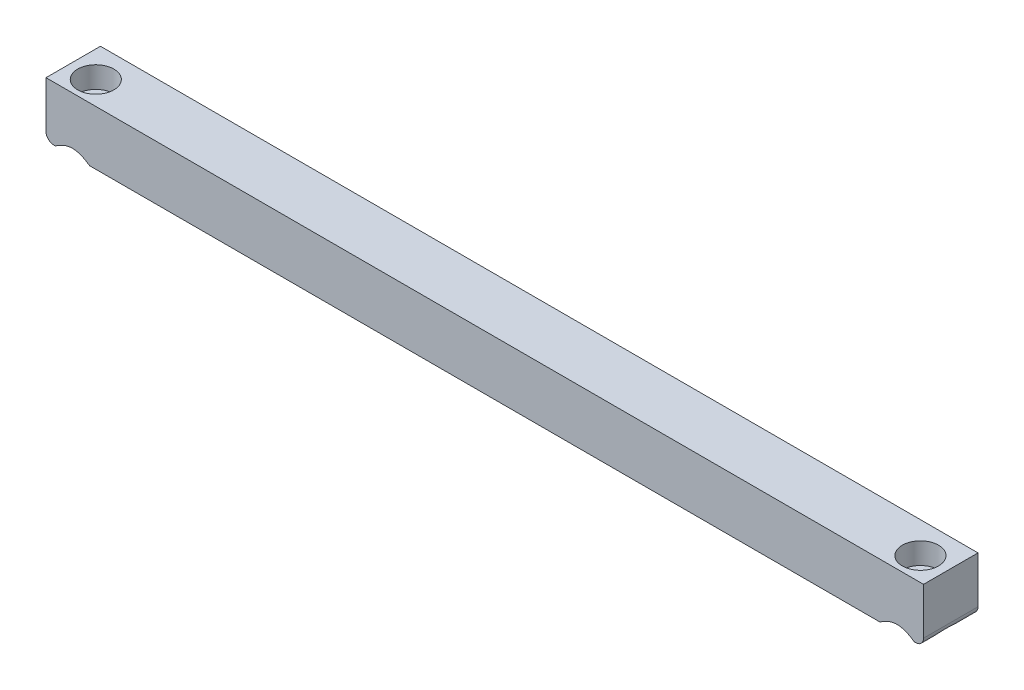
SolidWorks part; units mm, degrees
ref_plane "Front" through (0, 0, 0) normal (0, 0, 1) x (1, 0, 0)
ref_plane "Top" through (0, 0, 0) normal (0, 1, 0) x (1, 0, 0)
ref_plane "Right" through (0, 0, 0) normal (1, 0, 0) x (0, 0, -1)
sketch "Sketch1" plane through (0, 0, 0) normal (0, 1, 0) x (1, 0, 0)
  line L1 (0, 0) -> (112.8, 0)
  line L2 (0, 0) -> (0, 7)
  line L3 (0, 7) -> (112.8, 7)
  line L4 (112.8, 0) -> (112.8, 7)
  dimension "D1" = 112.8
  dimension "D2" = 7
extrude "Boss-Extrude1" add sketch "Sketch1" along normal blind 7
sketch "Sketch2" plane through (0, 0, 0) normal (0, -1, 0) x (1, 0, 0)
  line L0 (56.4, 0) -> (56.4, 24.6829) construction
  line L1 (0, 0) -> (112.8, 0) construction
hole_wizard "CSK for #4 Flat Head Machine Screw1" positions "Sketch3" profile "Sketch4" countersink size "#4" standard "ANSI Inch" end condition through all
sketch "Sketch3" plane through (0, 0, 0) normal (0, -1, 0) x (-1, 0, 0)
  line L0 (-56.4, 7) -> (-56.4, 30.7307) construction
  line L1 (-112.8, 7) -> (0, 7) construction
  line L4 (0, 0) -> (-112.8, 0) construction
  point P11 (-3.4, 3)
  point P15 (-109.4, 3)
  dimension "D1" = 3
  dimension "D3" = 53
sketch "Sketch4" plane through (109.4, 0, -3) normal (1, 0, 0) x (0, 0, -1)
  line L0 (0, 0) -> (0, 7)
  line L1 (0, 7) -> (1.4732, 7)
  line L2 (1.4732, 7) -> (1.4732, 2.5925)
  line L3 (1.4732, 2.5925) -> (3.7268, 0)
  line L5 (3.7268, 0) -> (0, 0)
  line L6 (-1.4732, 2.5925) -> (-3.7268, 0) construction
  line L11 (0, -6.35) -> (0, 107.95) construction
  dimension "Thru Hole Dia." = 2.9464
  dimension "Thru Hole Depth" = 7
  dimension "Near C'Sink Dia." = 7.4536
  dimension "Near C'Sink Angle" = 82
fillet "Fillet1" radius 1 4 edges at (0, 0, -5.763) (0, 0, -0.737) (112.8, 0, -0.737) (112.8, 0, -5.763)
sketch "Sketch5" plane through (0, 7, 0) normal (0, 1, 0) x (1, 0, 0)
  circle A0 centre (3.4, 3) radius 2.325
  dimension "D1" = 4.65
extrude "4-40 registration hole" cut sketch "Sketch5" against normal blind 2.75
ref_plane "mirror plane" through (56.4, 0, 0) normal (1, 0, 0) x (0, 0, -1)
mirror "Mirror1" about plane through (56.4, 0, 0) normal (1, 0, 0) of "4-40 registration hole"
